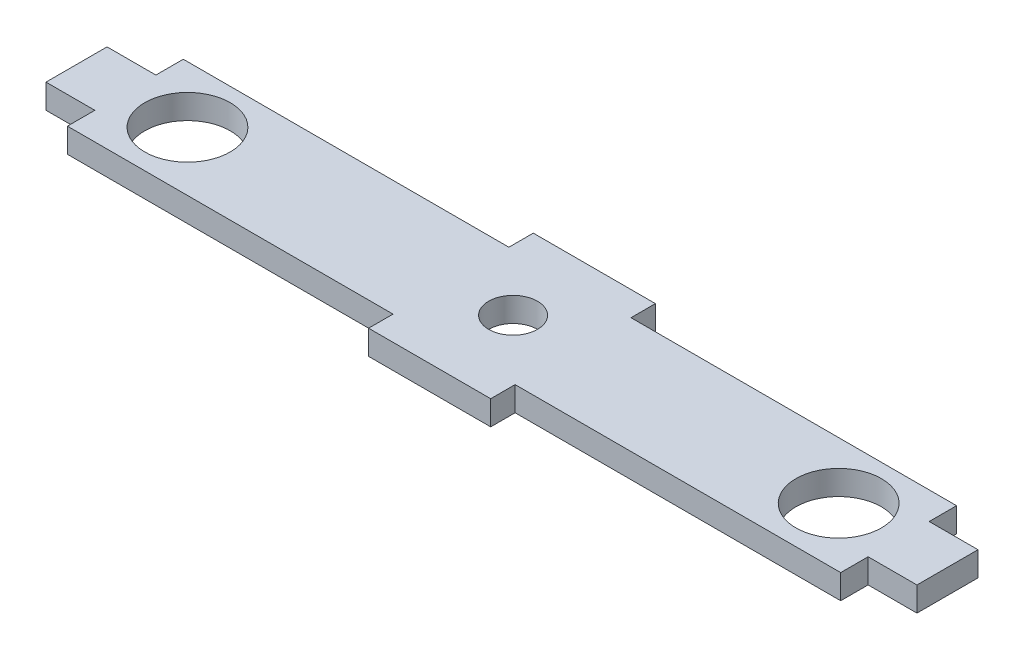
SolidWorks part; units mm, degrees
ref_plane "Front" through (0, 0, 0) normal (0, 0, 1) x (1, 0, 0)
ref_plane "Top" through (0, 0, 0) normal (0, 1, 0) x (1, 0, 0)
ref_plane "Right" through (0, 0, 0) normal (1, 0, 0) x (0, 0, -1)
sketch "Эскиз1" plane through (0, 0, 0) normal (0, 1, 0) x (1, 0, 0)
  line L0 (110.5788, 0.265) -> (-105.6913, 0.265) construction
  line L1 (-95, 14.235) -> (-15, 14.235)
  line L2 (-95, 14.235) -> (-95, 7.5)
  line L3 (-95, -14.235) -> (-15, -14.235)
  line L4 (95, 14.235) -> (95, 7.5)
  line L5 (-95, 14.235) -> (95, -14.235) construction
  line L6 (-95, -14.235) -> (95, 14.235) construction
  line L7 (-80, 48.7611) -> (-80, -31.1923) construction
  line L8 (80, 43.1247) -> (80, -42.2563) construction
  line L9 (0, 43.1247) -> (0, -49.9803) construction
  line L10 (-98.4497, 20.235) -> (101.9556, 20.235) construction
  line L11 (-98.4497, -20.235) -> (110.5788, -20.235) construction
  line L12 (15, 14.235) -> (95, 14.235)
  line L13 (-15, 20.235) -> (15, 20.235)
  line L14 (-15, 20.235) -> (-15, 14.235)
  line L16 (15, 20.235) -> (15, 14.235)
  line L17 (15, -14.235) -> (95, -14.235)
  line L19 (-15, -14.235) -> (-15, -20.235)
  line L20 (-15, -20.235) -> (15, -20.235)
  line L21 (15, -14.235) -> (15, -20.235)
  line L22 (0, 0) -> (111.9405, 0) construction
  line L23 (95, 7.5) -> (107, 7.5)
  line L27 (107, 7.5) -> (107, -7.5)
  line L28 (95, -7.5) -> (95, -14.235)
  line L29 (-95, -7.5) -> (-107, -7.5)
  line L30 (-107, 7.5) -> (-107, -7.5)
  line L31 (95, -7.5) -> (107, -7.5)
  line L32 (-95, 7.5) -> (-107, 7.5)
  line L33 (-95, -7.5) -> (-95, -14.235)
  circle A1 centre (-80, 0.265) radius 10.5
  circle A2 centre (80, 0.265) radius 10.5
  circle A3 centre (0, 0.265) radius 6
  point P0 (0, 0)
  point P24 (0, 14.235)
  point P25 (0, -14.235)
  point P36 (95, 0)
  dimension "D4" = 12
  dimension "D7" = 21
  dimension "D1" = 190
  dimension "D2" = 28.47
  dimension "D3" = 13.97
  dimension "D5" = 15
  dimension "D6" = 15
  dimension "D8" = 6
  dimension "D9" = 6
  dimension "D10" = 30
  dimension "D11" = 30
  dimension "D12" = 15
  dimension "D13" = 15
  dimension "D14" = 15
  dimension "D15" = 12
  dimension "D16" = 7.5
extrude "Бобышка-Вытянуть1" add sketch "Эскиз1" along normal blind 6
